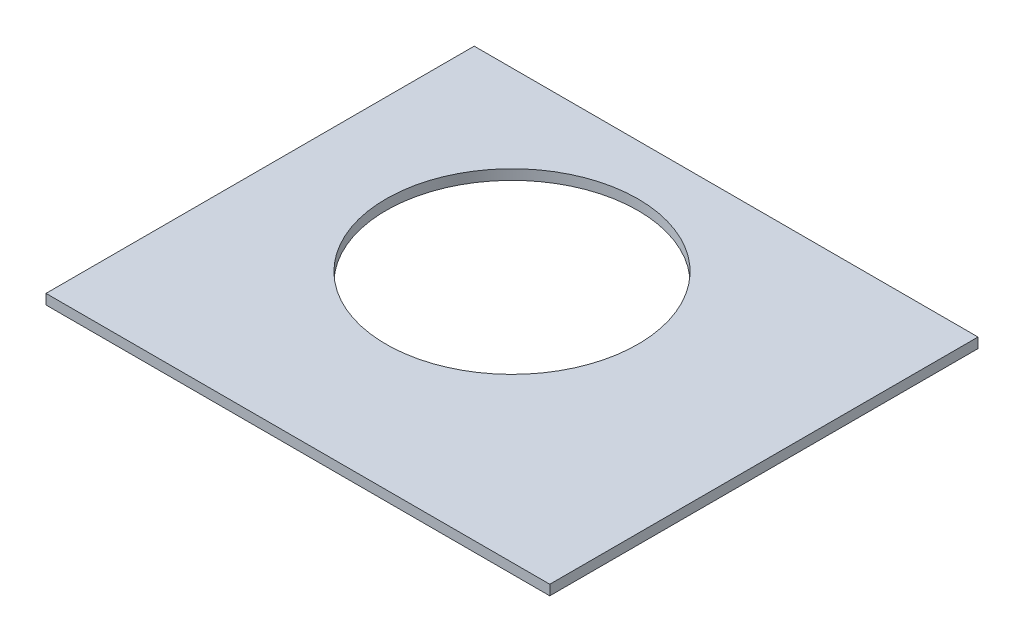
SolidWorks part; units mm, degrees
ref_plane "Front Plane" through (0, 0, 0) normal (0, 0, 1) x (1, 0, 0)
ref_plane "Top Plane" through (0, 0, 0) normal (0, 1, 0) x (1, 0, 0)
ref_plane "Right Plane" through (0, 0, 0) normal (1, 0, 0) x (0, 0, -1)
sketch "Sketch1" plane through (0, 0, 0) normal (0, 1, 0) x (1, 0, 0)
  line L1 (0, 0) -> (200, 0)
  line L2 (0, 0) -> (0, 170)
  line L3 (0, 170) -> (200, 170)
  line L4 (200, 0) -> (200, 170)
  dimension "D1" = 170
  dimension "D2" = 200
extrude "Boss-Extrude1" add sketch "Sketch1" along normal blind 4
sketch "Sketch3" plane through (0, 4, 0) normal (0, 1, 0) x (1, 0, 0)
  line L0 (0, 0) -> (20, 0)
  line L1 (0, 0) -> (200, 0) construction
  line L2 (20, 0) -> (20, 10)
  line L3 (0, 0) -> (0, 20)
  line L4 (0, 170) -> (0, 0) construction
  line L5 (0, 20) -> (10, 20)
  line L6 (10, 20) -> (10, 30) construction
  line L7 (5, 20) -> (5, 30)
  line L8 (15, 20) -> (15, 30)
  line L9 (20, 10) -> (30, 10) construction
  line L10 (20, 15) -> (30, 15)
  line L11 (20, 5) -> (30, 5)
  line L12 (0, 85) -> (200, 85) construction
  line L13 (200, 0) -> (200, 170) construction
  line L14 (100, 0) -> (100, 170) construction
  line L15 (200, 170) -> (0, 170) construction
  line L16 (10, 50) -> (10, 85) construction
  line L17 (5, 50) -> (5, 85)
  line L18 (15, 50) -> (15, 85)
  line L19 (50, 10) -> (70, 10) construction
  line L20 (50, 15) -> (70, 15)
  line L21 (50, 5) -> (70, 5)
  line L22 (190, 50) -> (190, 85) construction
  line L23 (195, 50) -> (195, 85)
  line L24 (185, 50) -> (185, 85)
  line L25 (190, 20) -> (190, 30) construction
  line L26 (195, 20) -> (195, 30)
  line L27 (185, 20) -> (185, 30)
  line L28 (180, 10) -> (170, 10) construction
  line L29 (180, 15) -> (170, 15)
  line L30 (180, 5) -> (170, 5)
  line L31 (150, 10) -> (130, 10) construction
  line L32 (150, 15) -> (130, 15)
  line L33 (150, 5) -> (130, 5)
  line L34 (190, 120) -> (190, 85) construction
  line L35 (195, 120) -> (195, 85)
  line L36 (185, 120) -> (185, 85)
  line L37 (170, 50) -> (115, 30) construction
  line L40 (168.2913, 54.699) -> (113.2913, 34.699)
  line L43 (171.7087, 45.301) -> (116.7087, 25.301)
  line L46 (170, 120) -> (115, 140) construction
  line L49 (168.2913, 115.301) -> (113.2913, 135.301)
  line L52 (171.7087, 124.699) -> (116.7087, 144.699)
  line L55 (10, 120) -> (10, 85) construction
  line L56 (5, 120) -> (5, 85)
  line L57 (15, 120) -> (15, 85)
  line L58 (200, 85) -> (200, 50) construction
  line L59 (200, 50) -> (0, 50) construction
  line L60 (200, 85) -> (200, 120) construction
  line L61 (200, 120) -> (0, 120) construction
  line L62 (30, 120) -> (85, 140) construction
  line L65 (31.7087, 115.301) -> (86.7087, 135.301)
  line L68 (28.2913, 124.699) -> (83.2913, 144.699)
  line L73 (30, 50) -> (85, 30) construction
  line L74 (31.7087, 54.699) -> (86.7087, 34.699)
  line L75 (28.2913, 45.301) -> (83.2913, 25.301)
  line L76 (100, 150) -> (100, 170) construction
  line L77 (95, 150) -> (95, 170)
  line L78 (105, 150) -> (105, 170)
  line L79 (60, 160) -> (60, 170) construction
  line L80 (55, 160) -> (55, 170)
  line L81 (65, 160) -> (65, 170)
  line L82 (140, 160) -> (140, 170) construction
  line L83 (145, 160) -> (145, 170)
  line L84 (135, 160) -> (135, 170)
  line L85 (10, 150) -> (10, 207.2046) construction
  line L86 (5, 150) -> (5, 207.2046)
  line L87 (15, 150) -> (15, 207.2046)
  line L88 (190, 150) -> (190, 207.2046) construction
  line L89 (195, 150) -> (195, 207.2046)
  line L90 (185, 150) -> (185, 207.2046)
  arc A1 (20, 10) -> (9.9962, 20) centre (21.0059, 21.0101) cw construction
  arc A2 (5.0171, 19.5432) -> (19.5451, 5.0207) centre (21.0059, 21.0101) ccw
  arc A3 (14.9753, 20.4568) -> (20.4549, 14.9793) centre (21.0059, 21.0101) ccw
  arc A4 (14.9753, 20.4568) -> (5.0171, 19.5432) centre (9.9962, 20) ccw
  arc A5 (19.5451, 5.0207) -> (20.4549, 14.9793) centre (20, 10) ccw
  arc A6 (5, 20) -> (15, 20) centre (10, 20) ccw
  arc A7 (15, 30) -> (5, 30) centre (10, 30) ccw
  arc A8 (20, 15) -> (20, 5) centre (20, 10) ccw
  arc A9 (30, 5) -> (30, 15) centre (30, 10) ccw
  arc A10 (5, 50) -> (15, 50) centre (10, 50) ccw
  arc A11 (15, 85) -> (5, 85) centre (10, 85) ccw
  arc A12 (50, 15) -> (50, 5) centre (50, 10) ccw
  arc A13 (70, 5) -> (70, 15) centre (70, 10) ccw
  arc A14 (195, 50) -> (185, 50) centre (190, 50) cw
  arc A15 (185, 85) -> (195, 85) centre (190, 85) cw
  arc A16 (195, 20) -> (185, 20) centre (190, 20) cw
  arc A17 (185, 30) -> (195, 30) centre (190, 30) cw
  arc A18 (180, 10) -> (190.0038, 20) centre (178.9941, 21.0101) ccw construction
  arc A19 (194.9829, 19.5432) -> (180.4549, 5.0207) centre (178.9941, 21.0101) cw
  arc A20 (185.0247, 20.4568) -> (179.5451, 14.9793) centre (178.9941, 21.0101) cw
  arc A21 (185.0247, 20.4568) -> (194.9829, 19.5432) centre (190.0038, 20) cw
  arc A22 (180.4549, 5.0207) -> (179.5451, 14.9793) centre (180, 10) cw
  arc A23 (180, 15) -> (180, 5) centre (180, 10) cw
  arc A24 (170, 5) -> (170, 15) centre (170, 10) cw
  arc A25 (150, 15) -> (150, 5) centre (150, 10) cw
  arc A26 (130, 5) -> (130, 15) centre (130, 10) cw
  arc A27 (195, 120) -> (185, 120) centre (190, 120) ccw
  arc A28 (185, 85) -> (195, 85) centre (190, 85) ccw
  circle A31 centre (100, 85) radius 50
  arc A44 (168.2913, 54.699) -> (171.7087, 45.301) centre (170, 50) cw
  arc A51 (5, 120) -> (15, 120) centre (10, 120) cw
  arc A52 (15, 85) -> (5, 85) centre (10, 85) cw
  arc A63 (31.7087, 54.699) -> (28.2913, 45.301) centre (30, 50) ccw
  arc A64 (83.2913, 25.301) -> (86.7087, 34.699) centre (85, 30) ccw
  arc A65 (116.7087, 25.301) -> (113.2913, 34.699) centre (115, 30) cw
  arc A66 (168.2913, 115.301) -> (171.7087, 124.699) centre (170, 120) ccw
  arc A67 (116.7087, 144.699) -> (113.2913, 135.301) centre (115, 140) ccw
  arc A68 (31.7087, 115.301) -> (28.2913, 124.699) centre (30, 120) cw
  arc A69 (83.2913, 144.699) -> (86.7087, 135.301) centre (85, 140) cw
  arc A70 (95, 150) -> (105, 150) centre (100, 150) ccw
  arc A71 (105, 170) -> (95, 170) centre (100, 170) ccw
  arc A72 (55, 160) -> (65, 160) centre (60, 160) ccw
  arc A73 (65, 170) -> (55, 170) centre (60, 170) ccw
  arc A74 (145, 160) -> (135, 160) centre (140, 160) cw
  arc A75 (135, 170) -> (145, 170) centre (140, 170) cw
  arc A76 (5, 150) -> (15, 150) centre (10, 150) ccw
  arc A77 (15, 207.2046) -> (5, 207.2046) centre (10, 207.2046) ccw
  arc A78 (195, 150) -> (185, 150) centre (190, 150) cw
  arc A79 (185, 207.2046) -> (195, 207.2046) centre (190, 207.2046) cw
  point P12 (13.1897, 13.1909)
  point P17 (10, 25)
  point P25 (25, 10)
  point P40 (10, 67.5)
  point P47 (60, 10)
  point P54 (190, 67.5)
  point P61 (190, 25)
  point P69 (186.8103, 13.1909)
  point P76 (175, 10)
  point P83 (140, 10)
  point P90 (190, 102.5)
  point P99 (142.5, 40)
  point P106 (142.5, 130)
  point P113 (57.5, 130)
  point P119 (100, 160)
  point P124 (60, 165)
  point P133 (140, 165)
  point P140 (10, 178.6023)
  point P147 (190, 178.6023)
  point P155 (10, 102.5)
  point P191 (57.5, 40)
  line M15 (200, 170) -> (0, 170)
  dimension "D4" = 5
  dimension "D8" = 5
  dimension "D11" = 5
  dimension "D16" = 100
  dimension "D19" = 5
  dimension "D22" = 5
  dimension "D24" = 16.0559
  dimension "D29" = 10
  dimension "D30" = 20
  dimension "D31" = 5
  dimension "D26" = 5
  dimension "D27" = 5
  dimension "D1" = 20
  dimension "D2" = 20
  dimension "D3" = 10
  dimension "D5" = 5
  dimension "D6" = 10
  dimension "D7" = 10
  dimension "D9" = 35
  dimension "D10" = 20
  dimension "D12" = 20
  dimension "D13" = 20
  dimension "D14" = 0
  dimension "D15" = 30
  dimension "D17" = 15
  dimension "D18" = 0
  dimension "D20" = 30
  dimension "D21" = 30
  dimension "D23" = 10
  dimension "D25" = 21.0101
  dimension "D28" = 5
  dimension "D32" = 30
extrude "Boss-Extrude2" add sketch "Sketch3" along normal blind 6 contours A26 L33 A25 L32 | A24 L30 A22 A20 L29 | A20 A21 L26 A17 L27 | A15 L24 A14 L23 | A65 L43 A44 L40 | L75 A64 L74 A63 | L8 A7 L7 A4 A3 | L11 A9 L10 A3 A5 | L21 A13 L20 A12 | L18 A11 L17 A10 | A52 L57 A51 L56 | L86 A76 L87 M15 | L80 A72 L81 M15 | L77 A70 L78 M15 | A74 L83 L84 M15 | A78 L89 L90 M15 | L36 A28 L35 A27 | L52 A67 L49 A66 | A69 L68 A68 L65 | A19 A22 A20 A21 | A2 A5 A3 A4 rebuild error yes
sketch "Sketch7" plane through (0, 0, 0) normal (0, 1, 0) x (1, 0, 0)
  line L0 (0, 0) -> (20, 0)
  line L2 (20, 0) -> (20, 10)
  line L3 (0, 0) -> (0, 20)
  line L5 (0, 20) -> (10, 20)
  line L6 (10, 20) -> (10, 30) construction
  line L7 (5, 20) -> (5, 30)
  line L8 (15, 20) -> (15, 30)
  line L9 (20, 10) -> (30, 10) construction
  line L10 (20, 15) -> (30, 15)
  line L11 (20, 5) -> (30, 5)
  line L12 (0, 100) -> (170, 100) construction
  line L14 (85, 0) -> (85, 200) construction
  line L16 (10, 50) -> (10, 85) construction
  line L17 (5, 50) -> (5, 85)
  line L18 (15, 50) -> (15, 85)
  line L19 (50, 10) -> (70, 10) construction
  line L20 (50, 15) -> (70, 15)
  line L21 (50, 5) -> (70, 5)
  line L22 (160, 50) -> (160, 85) construction
  line L23 (165, 50) -> (165, 85)
  line L24 (155, 50) -> (155, 85)
  line L25 (160, 20) -> (160, 30) construction
  line L26 (165, 20) -> (165, 30)
  line L27 (155, 20) -> (155, 30)
  line L28 (150, 10) -> (140, 10) construction
  line L29 (150, 15) -> (140, 15)
  line L30 (150, 5) -> (140, 5)
  line L31 (120, 10) -> (100, 10) construction
  line L32 (120, 15) -> (100, 15)
  line L33 (120, 5) -> (100, 5)
  line L34 (160, 150) -> (160, 115) construction
  line L35 (165, 150) -> (165, 115)
  line L36 (155, 150) -> (155, 115)
  line L37 (140, 50) -> (100, 30) construction
  line L40 (137.7639, 54.4721) -> (97.7639, 34.4721)
  line L43 (142.2361, 45.5279) -> (102.2361, 25.5279)
  line L46 (140, 150) -> (100, 170) construction
  line L49 (137.7639, 145.5279) -> (97.7639, 165.5279)
  line L52 (142.2361, 154.4721) -> (102.2361, 174.4721)
  line L55 (10, 150) -> (10, 115) construction
  line L56 (5, 150) -> (5, 115)
  line L57 (15, 150) -> (15, 115)
  line L58 (170, 100) -> (170, 50) construction
  line L59 (170, 50) -> (0, 50) construction
  line L60 (170, 100) -> (170, 150) construction
  line L61 (170, 150) -> (0, 150) construction
  line L62 (30, 150) -> (70, 170) construction
  line L65 (32.2361, 145.5279) -> (72.2361, 165.5279)
  line L68 (27.7639, 154.4721) -> (67.7639, 174.4721)
  line L73 (30, 50) -> (70, 30) construction
  line L74 (32.2361, 54.4721) -> (72.2361, 34.4721)
  line L75 (27.7639, 45.5279) -> (67.7639, 25.5279)
  line L76 (85, 180) -> (85, 200) construction
  line L77 (80, 180) -> (80, 200)
  line L78 (90, 180) -> (90, 200)
  line L79 (60, 190) -> (60, 200) construction
  line L80 (55, 190) -> (55, 200)
  line L81 (65, 190) -> (65, 200)
  line L82 (110, 190) -> (110, 200) construction
  line L83 (115, 190) -> (115, 200)
  line L84 (105, 190) -> (105, 200)
  line L85 (10, 180) -> (10, 207.2046) construction
  line L86 (5, 180) -> (5, 207.2046)
  line L87 (15, 180) -> (15, 207.2046)
  line L88 (160, 180) -> (160, 207.2046) construction
  line L89 (165, 180) -> (165, 207.2046)
  line L90 (155, 180) -> (155, 207.2046)
  arc A1 (20, 10) -> (9.9962, 20) centre (21.0059, 21.0101) cw construction
  arc A2 (5.0171, 19.5432) -> (19.5451, 5.0207) centre (21.0059, 21.0101) ccw
  arc A3 (14.9753, 20.4568) -> (20.4549, 14.9793) centre (21.0059, 21.0101) ccw
  arc A4 (14.9753, 20.4568) -> (5.0171, 19.5432) centre (9.9962, 20) ccw
  arc A5 (19.5451, 5.0207) -> (20.4549, 14.9793) centre (20, 10) ccw
  arc A6 (5, 20) -> (15, 20) centre (10, 20) ccw
  arc A7 (15, 30) -> (5, 30) centre (10, 30) ccw
  arc A8 (20, 15) -> (20, 5) centre (20, 10) ccw
  arc A9 (30, 5) -> (30, 15) centre (30, 10) ccw
  arc A10 (5, 50) -> (15, 50) centre (10, 50) ccw
  arc A11 (15, 85) -> (5, 85) centre (10, 85) ccw
  arc A12 (50, 15) -> (50, 5) centre (50, 10) ccw
  arc A13 (70, 5) -> (70, 15) centre (70, 10) ccw
  arc A14 (165, 50) -> (155, 50) centre (160, 50) cw
  arc A15 (155, 85) -> (165, 85) centre (160, 85) cw
  arc A16 (165, 20) -> (155, 20) centre (160, 20) cw
  arc A17 (155, 30) -> (165, 30) centre (160, 30) cw
  arc A18 (150, 10) -> (160.0038, 20) centre (148.9941, 21.0101) ccw construction
  arc A19 (164.9829, 19.5432) -> (150.4549, 5.0207) centre (148.9941, 21.0101) cw
  arc A20 (155.0247, 20.4568) -> (149.5451, 14.9793) centre (148.9941, 21.0101) cw
  arc A21 (155.0247, 20.4568) -> (164.9829, 19.5432) centre (160.0038, 20) cw
  arc A22 (150.4549, 5.0207) -> (149.5451, 14.9793) centre (150, 10) cw
  arc A23 (150, 15) -> (150, 5) centre (150, 10) cw
  arc A24 (140, 5) -> (140, 15) centre (140, 10) cw
  arc A25 (120, 15) -> (120, 5) centre (120, 10) cw
  arc A26 (100, 5) -> (100, 15) centre (100, 10) cw
  arc A27 (165, 150) -> (155, 150) centre (160, 150) ccw
  arc A28 (155, 115) -> (165, 115) centre (160, 115) ccw
  circle A31 centre (85, 100) radius 50
  arc A44 (137.7639, 54.4721) -> (142.2361, 45.5279) centre (140, 50) cw
  arc A51 (5, 150) -> (15, 150) centre (10, 150) cw
  arc A52 (15, 115) -> (5, 115) centre (10, 115) cw
  arc A63 (32.2361, 54.4721) -> (27.7639, 45.5279) centre (30, 50) ccw
  arc A64 (67.7639, 25.5279) -> (72.2361, 34.4721) centre (70, 30) ccw
  arc A65 (102.2361, 25.5279) -> (97.7639, 34.4721) centre (100, 30) cw
  arc A66 (137.7639, 145.5279) -> (142.2361, 154.4721) centre (140, 150) ccw
  arc A67 (102.2361, 174.4721) -> (97.7639, 165.5279) centre (100, 170) ccw
  arc A68 (32.2361, 145.5279) -> (27.7639, 154.4721) centre (30, 150) cw
  arc A69 (67.7639, 174.4721) -> (72.2361, 165.5279) centre (70, 170) cw
  arc A70 (80, 180) -> (90, 180) centre (85, 180) ccw
  arc A71 (90, 200) -> (80, 200) centre (85, 200) ccw
  arc A72 (55, 190) -> (65, 190) centre (60, 190) ccw
  arc A73 (65, 200) -> (55, 200) centre (60, 200) ccw
  arc A74 (115, 190) -> (105, 190) centre (110, 190) cw
  arc A75 (105, 200) -> (115, 200) centre (110, 200) cw
  arc A76 (5, 180) -> (15, 180) centre (10, 180) ccw
  arc A77 (15, 207.2046) -> (5, 207.2046) centre (10, 207.2046) ccw
  arc A78 (165, 180) -> (155, 180) centre (160, 180) cw
  arc A79 (155, 207.2046) -> (165, 207.2046) centre (160, 207.2046) cw
  point P12 (13.1897, 13.1909)
  point P17 (10, 25)
  point P25 (25, 10)
  point P40 (10, 67.5)
  point P47 (60, 10)
  point P54 (160, 67.5)
  point P61 (160, 25)
  point P69 (156.8103, 13.1909)
  point P76 (145, 10)
  point P83 (110, 10)
  point P90 (160, 132.5)
  point P99 (120, 40)
  point P106 (120, 160)
  point P113 (50, 160)
  point P119 (85, 190)
  point P124 (60, 195)
  point P133 (110, 195)
  point P140 (10, 193.6023)
  point P147 (160, 193.6023)
  point P155 (10, 132.5)
  point P191 (50, 40)
  dimension "D4" = 5
  dimension "D8" = 5
  dimension "D11" = 5
  dimension "D16" = 100
  dimension "D19" = 5
  dimension "D22" = 5
  dimension "D24" = 16.0559
  dimension "D29" = 10
  dimension "D31" = 5
  dimension "D26" = 5
  dimension "D27" = 5
  dimension "D1" = 20
  dimension "D2" = 20
  dimension "D3" = 10
  dimension "D5" = 5
  dimension "D6" = 10
  dimension "D7" = 10
  dimension "D9" = 35
  dimension "D10" = 20
  dimension "D12" = 20
  dimension "D13" = 20
  dimension "D14" = 15
  dimension "D15" = 15
  dimension "D17" = 15
  dimension "D18" = 0
  dimension "D32" = 30
extrude "Cut-Extrude9" cut sketch "Sketch7" along normal blind 6 contours A31
